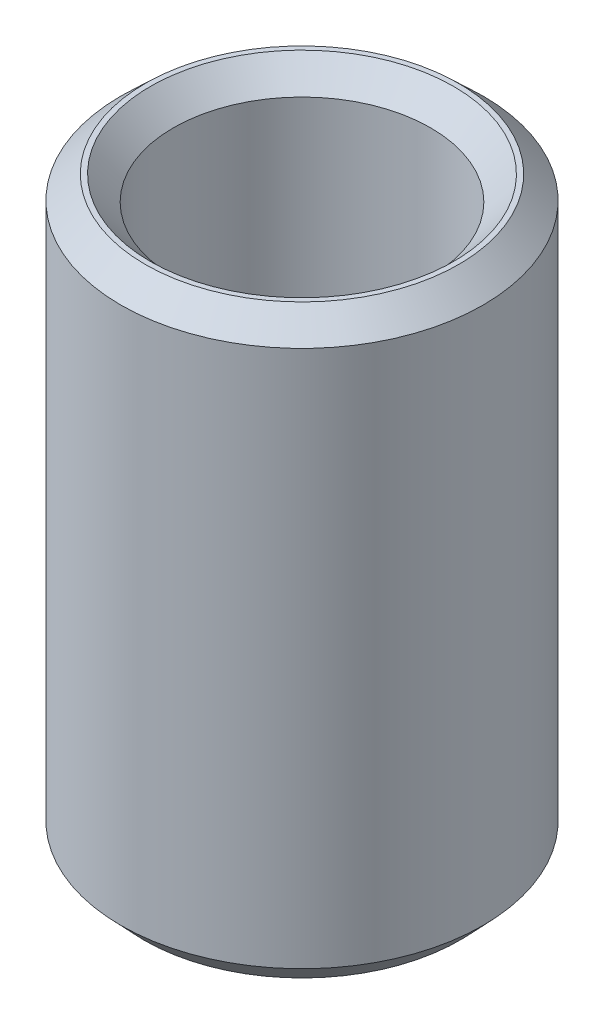
SolidWorks part; units mm, degrees
ref_plane "Front Plane" through (0, 0, 0) normal (0, 0, 1) x (1, 0, 0)
ref_plane "Top Plane" through (0, 0, 0) normal (0, 1, 0) x (1, 0, 0)
ref_plane "Right Plane" through (0, 0, 0) normal (1, 0, 0) x (0, 0, -1)
sketch "Sketch1" plane through (0, 0, 0) normal (0, 1, 0) x (1, 0, 0)
  circle A0 centre (0, 0) radius 15
  dimension "SLEEVE_OD" = 30
extrude "Boss-Extrude1" add sketch "Sketch1" along normal blind 48.4215
sketch "Sketch2" plane through (0, 0, 0) normal (0, 1, 0) x (1, 0, 0)
  circle A0 centre (0, 0) radius 10.6527
  dimension "BORE_D" = 21.3055
extrude "Cut-Extrude1" cut sketch "Sketch2" along normal through all
chamfer "Chamfer1" distance 1.909 angle 46.529 4 edges at (0, 48.4215, 10.6527) (0, 0, 10.6527) (0, 0, 15) (0, 48.4215, 15) first distance on face at (0, 48.4215, 10.6527) first distance on face at (0, 0, 10.6527) first distance on face at (0, 48.4215, 15)
